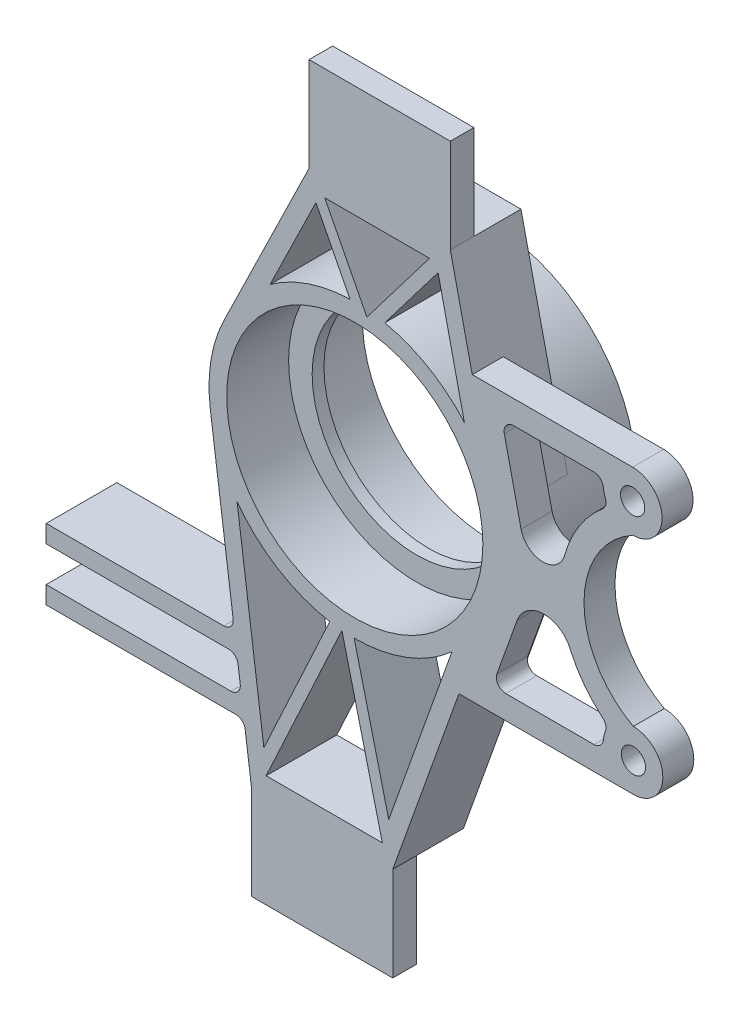
SolidWorks part; units mm, degrees
ref_plane "Front" through (0, 0, 0) normal (0, 0, 1) x (1, 0, 0)
ref_plane "Top" through (0, 0, 0) normal (0, 1, 0) x (1, 0, 0)
ref_plane "Right" through (0, 0, 0) normal (1, 0, 0) x (0, 0, -1)
sketch "Sketch1" plane through (0, 0, 0) normal (0, 0, 1) x (1, 0, 0)
  line L0 (-1549.0237, 297.4698) -> (-1587.1237, 297.4698) construction
  line L2 (-1564.5503, 119.6698) -> (-1602.6503, 119.6698) construction
  line L4 (-1602.6503, 132.3698) -> (-1602.6503, 106.9698)
  line L5 (-1602.6503, 106.9698) -> (-1564.5503, 106.9698)
  line L6 (-1564.5503, 132.3698) -> (-1564.5503, 106.9698)
  line L7 (-1602.6503, 132.3698) -> (-1564.5503, 132.3698)
  line L8 (-1549.0237, 310.1698) -> (-1549.0237, 284.7698)
  line L9 (-1549.0237, 284.7698) -> (-1587.1237, 284.7698)
  line L10 (-1587.1237, 310.1698) -> (-1587.1237, 284.7698)
  line L11 (-1587.1237, 310.1698) -> (-1549.0237, 310.1698)
  line L12 (-1568.0737, 297.4698) -> (-1583.6003, 119.6698) construction
  line L13 (-1587.1237, 284.7698) -> (-1610.118, 237.6971)
  line L14 (-1613.758, 215.2219) -> (-1602.6503, 132.3698)
  line L15 (-1564.5503, 132.3698) -> (-1537.7886, 207.2101)
  line L16 (-1536.4581, 229.099) -> (-1549.0237, 284.7698)
  line L17 (-1585.2805, 277.6924) -> (-1597.6073, 252.4577)
  line L18 (-1576.0758, 259.7306) -> (-1585.2805, 277.6924)
  line L19 (-1552.3332, 277.8017) -> (-1566.7144, 258.9107)
  line L20 (-1545.2328, 246.3443) -> (-1552.3332, 277.8017)
  line L21 (-1599.317, 143.3478) -> (-1606.5457, 197.267)
  line L22 (-1581.5499, 181.7222) -> (-1599.317, 143.3478)
  line L23 (-1565.6496, 143.4402) -> (-1574.9613, 181.1386)
  line L24 (-1548.5876, 191.1547) -> (-1565.6496, 143.4402)
  line L25 (-1577.8052, 186.0317) -> (-1602.6503, 132.3698) construction
  line L26 (-1564.5503, 132.3698) -> (-1577.8052, 186.0317) construction
  line L27 (-1578.2629, 181.2647) -> (-1598.6959, 137.1323)
  line L28 (-1598.6959, 137.1323) -> (-1567.3619, 137.1323)
  line L29 (-1567.3619, 137.1323) -> (-1578.2629, 181.2647)
  line L30 (-1571.5314, 257.8247) -> (-1582.8992, 280.0073)
  line L31 (-1582.8992, 280.0073) -> (-1554.6444, 280.0073)
  line L32 (-1554.6444, 280.0073) -> (-1571.5314, 257.8247)
  line L33 (-1587.1237, 284.7698) -> (-1571.7948, 254.8578) construction
  line L34 (-1571.7948, 254.8578) -> (-1549.0237, 284.7698) construction
  circle A0 centre (-1574.8, 220.4448) radius 34.544
  circle A1 centre (-1574.8, 220.4448) radius 39.3065 construction
  arc A2 (-1610.118, 237.6971) -> (-1613.758, 215.2219) centre (-1574.8, 220.4448) ccw
  arc A3 (-1606.5457, 197.267) -> (-1581.5499, 181.7222) centre (-1574.8, 220.4448) ccw
  arc A4 (-1574.9613, 181.1386) -> (-1548.5876, 191.1547) centre (-1574.8, 220.4448) ccw
  arc A6 (-1537.7886, 207.2101) -> (-1536.4581, 229.099) centre (-1574.8, 220.4448) ccw
  arc A7 (-1545.2328, 246.3443) -> (-1566.7144, 258.9107) centre (-1574.8, 220.4448) ccw
  arc A8 (-1576.0758, 259.7306) -> (-1597.6073, 252.4577) centre (-1574.8, 220.4448) ccw
  point P0 (-1568.0737, 297.4698)
  point P1 (-1583.6003, 119.6698)
  point P3 (-1574.8, 220.4448)
  point P9 (-1568.0737, 297.4698)
  point P12 (-1583.6003, 119.6698)
  point P15 (-1602.6503, 119.6698)
  point P19 (-1564.5503, 119.6698)
  point P20 (-1549.0237, 297.4698)
  point P24 (-1587.1237, 297.4698)
  point P45 (-1571.7948, 254.8578)
  point P47 (-1577.8052, 186.0317)
  point P57 (-1551.1695, 169.79)
  dimension "D3" = 69.088
  dimension "D1" = 38.1
  dimension "D2" = 25.4
  dimension "D4" = 4.7625
  dimension "D5" = 4.7625
  dimension "D6" = 4.7625
  dimension "D7" = 4.7625
  dimension "D8" = 4.7625
  dimension "D9" = 4.7625
  dimension "D10" = 1.5875
  dimension "D11" = 1.5875
  dimension "D12" = 1.5875
  dimension "D13" = 1.5875
  dimension "D14" = 4.7625
  dimension "D15" = 1.5875
  dimension "D16" = 1.5875
  dimension "D17" = 1.5875
  dimension "D18" = 1.5875
extrude "Boss-Extrude1" add sketch "Sketch1" along normal blind 6.35 and the other way blind 12.7 contours L15 A6 L16 L9 L13 A2 L14 L7 L23 A4 L24 L21 A3 L22 L31 L32 L30 L29 L28 L27 A0 L20 A7 L19 L18 A8 L17 | L11 L10 L9 L8 | L7 L4 L5 L6 region at (-1583.6003, 119.6698, 0) region at (-1606.5045, 174.0237, 0) region at (-1568.0737, 297.4698, 0)
sketch "Sketch2" plane through (0, 0, -12.7) normal (0, 0, -1) x (-1, 0, 0)
  line L1 (1549.0237, 310.1698) -> (1587.1237, 310.1698)
  line L2 (1549.0237, 310.1698) -> (1549.0237, 284.7698)
  line L3 (1549.0237, 284.7698) -> (1587.1237, 284.7698)
  line L4 (1587.1237, 310.1698) -> (1587.1237, 284.7698)
  line L5 (1564.5503, 132.3698) -> (1602.6503, 132.3698)
  line L6 (1564.5503, 132.3698) -> (1564.5503, 106.9698)
  line L7 (1564.5503, 106.9698) -> (1602.6503, 106.9698)
  line L8 (1602.6503, 132.3698) -> (1602.6503, 106.9698)
extrude "Cut-Extrude1" cut sketch "Sketch2" against normal up to surface (12.7 mm away) up to plane "Front"
sketch "Sketch3" plane through (0, 0, -12.7) normal (0, 0, -1) x (-1, 0, 0)
  circle A0 centre (1574.8, 220.4448) radius 34.544
  circle A1 centre (1574.8, 220.4448) radius 39.3065
  arc A4 (1613.758, 215.2219) -> (1610.118, 237.6971) centre (1574.8, 220.4448) ccw construction
  circle A5 centre (1574.8, 220.4448) radius 34.544 construction
extrude "Boss-Extrude3" add sketch "Sketch3" along normal offset from surface (17.526 mm away) 36.576 up to face at (-1562.7563, 171.0953, 6.35)
ref_plane "Wheel bearing Mid Plane" through (0, 0, -11.938) normal (0, 0, -1) x (-1, 0, 0)
sketch "Sketch4" plane through (0, 0, -11.938) normal (0, 0, -1) x (-1, 0, 0)
  circle A0 centre (1574.8, 220.4448) radius 28.194
  circle A1 centre (1574.8, 220.4448) radius 34.544
  circle A2 centre (1574.8, 220.4448) radius 34.544 construction
  dimension "D1" = 6.35
extrude "Boss-Extrude4" add sketch "Sketch4" along normal mid plane 3.175
sketch3d "3DSketch30"
  point P0 (-1499.6605, 190.2188, -11.938)
  point P1 (-1499.87, 250.6708, -11.938)
sketch "Sketch12" plane through (0, 0, -11.938) normal (0, 0, -1) x (-1, 0, 0)
  line L0 (1574.8, 248.6388) -> (1574.8, 192.2508) construction
  line L1 (1602.994, 220.4448) -> (1546.606, 220.4448) construction
  line L2 (1574.8, 220.4448) -> (1510.8834, 254.4298) construction
  line L3 (1574.8, 220.4448) -> (1510.8834, 186.4597) construction
  line L4 (1510.8834, 254.4298) -> (1496.306, 262.1808)
  line L5 (1510.8834, 186.4597) -> (1496.306, 178.7088)
  line L6 (1510.8834, 254.4298) -> (1542.1755, 254.4298)
  line L7 (1536.4581, 229.099) -> (1549.0237, 284.7698) construction
  line L8 (1496.306, 262.1808) -> (1543.925, 262.1808)
  line L9 (1496.306, 178.7088) -> (1547.9802, 178.7088)
  line L10 (1564.5503, 132.3698) -> (1537.7886, 207.2101) construction
  line L11 (1510.8834, 186.4597) -> (1545.2086, 186.4597)
  line L12 (26.8478, 175.2501) -> (101.9873, 145.0241)
  circle A0 centre (1574.8, 220.4448) radius 28.194 construction
  circle A1 centre (1574.8, 220.4448) radius 101.6 construction
  arc A2 (1510.8834, 254.4298) -> (1510.8834, 186.4597) centre (1574.8, 220.4448) ccw
  arc A3 (1496.306, 262.1808) -> (1496.306, 178.7088) centre (1574.8, 220.4448) ccw
  dimension "D1" = 203.2
  dimension "D2" = 28
  dimension "D3" = 72.39
  dimension "D4" = 28
  dimension "D5" = 72.39
  dimension "D6" = 16.51
sketch "Sketch16" plane through (0, 0, -11.938) normal (0, 0, -1) x (-1, 0, 0)
  line L0 (1473.2114, 206.0921) -> (1477.0541, 201.975)
  line L1 (1493.6277, 256.6714) -> (1490.0932, 252.8846)
  line L2 (1477.0541, 238.9146) -> (1473.2114, 234.7975)
  line L3 (1507.9155, 220.4448) -> (1487.5955, 220.4448) construction
  line L4 (1477.0541, 238.9146) -> (1477.0541, 252.8846)
  line L5 (1477.0541, 252.8846) -> (1490.0932, 252.8846)
  line L6 (1477.0541, 188.005) -> (1490.0932, 188.005)
  line L7 (1477.0541, 201.975) -> (1477.0541, 188.005)
  line L8 (1490.0932, 188.005) -> (1493.6277, 184.2181)
  line L9 (1499.6605, 250.6708) -> (1499.6605, 190.2188)
  line L11 (1602.994, 220.4448) -> (1546.606, 220.4448) construction
  line L12 (1499.6605, 250.6708) -> (1574.8, 220.4448) construction
  arc A0 (1493.6277, 184.2181) -> (1507.2706, 194.0253) centre (1499.6605, 190.2188) ccw
  arc A1 (1506.6529, 213.3937) -> (1506.6529, 227.4959) centre (1487.5955, 220.4448) ccw
  arc A2 (1507.2706, 246.8643) -> (1493.6277, 256.6714) centre (1499.6605, 250.6708) ccw
  arc A3 (1473.2114, 234.7975) -> (1473.2114, 206.0921) centre (1487.5955, 220.4448) ccw
  spline S0 degree 3 poles (1507.2706, 194.0253) (1506.8889, 194.7187) (1506.243, 196.1544) (1505.3287, 199.2948) (1504.9785, 202.6898) (1505.1113, 206.1293) (1505.4307, 208.6738) (1505.8589, 210.7151) (1506.288, 212.2791) (1506.5252, 213.0215) (1506.6529, 213.3937) knots 0 0 0 0 0.124858 0.249716 0.499432 0.62429 0.749148 0.874006 0.936435 0.998864 0.998864 0.998864 0.998864
  spline S1 degree 3 poles (1506.6529, 227.4959) (1506.5252, 227.868) (1506.288, 228.6104) (1505.8589, 230.1745) (1505.4307, 232.2158) (1505.1113, 234.7602) (1504.9785, 238.1998) (1505.3287, 241.5948) (1506.243, 244.7352) (1506.8889, 246.1709) (1507.2706, 246.8643) knots 0.001136 0.001136 0.001136 0.001136 0.063565 0.125994 0.250852 0.37571 0.500568 0.750284 0.875142 1 1 1 1
sketch "Sketch50" plane through (0, 0, 0) normal (0, 0, 1) x (1, 0, 0)
  line L0 (-1506.3544, 246.093) -> (-1502.6922, 240.9055) construction
  line L1 (-1536.4581, 229.099) -> (-1549.0237, 284.7698) construction
  line L2 (-1535.1787, 252.2583) -> (-1535.1787, 258.6083) construction
  line L3 (-1564.5503, 132.3698) -> (-1537.7886, 207.2101) construction
  line L4 (-1541.3271, 250.6708) -> (-1536.4581, 229.099)
  line L5 (-1543.8644, 190.2188) -> (-1537.7886, 207.2101)
  line L6 (-1499.87, 258.6083) -> (-1543.1187, 258.6083)
  line L7 (-1543.1187, 258.6083) -> (-1541.3271, 250.6708)
  line L8 (-1499.6605, 182.2813) -> (-1546.7028, 182.2813)
  line L9 (-1546.7028, 182.2813) -> (-1543.8644, 190.2188)
  line L10 (-1499.87, 250.6708) -> (-1499.6605, 190.2188) construction
  line L11 (-1535.1787, 252.2583) -> (-1507.6471, 252.2583)
  line L12 (-1535.1787, 252.2583) -> (-1529.9514, 229.099)
  line L13 (-1550.5652, 220.4448) -> (-1448.9652, 220.4448) construction
  line L14 (-1506.3544, 194.7965) -> (-1502.6922, 199.9841) construction
  line L15 (-1535.1787, 252.2583) -> (-1541.3271, 250.6708) construction
  line L16 (-1507.6471, 188.6313) -> (-1537.6883, 188.6313)
  line L17 (-1537.6883, 188.6313) -> (-1537.6883, 182.2813) construction
  line L18 (-1537.6883, 188.6313) -> (-1531.0448, 207.2101)
  line L19 (-1537.6883, 188.6313) -> (-1543.6676, 190.7694) construction
  arc A0 (-1536.4581, 229.099) -> (-1537.7886, 207.2101) centre (-1574.8, 220.4448) cw
  arc A1 (-1499.87, 258.6083) -> (-1499.8425, 242.7333) centre (-1499.87, 250.6708) cw
  arc A2 (-1499.6605, 182.2813) -> (-1499.688, 198.1562) centre (-1499.6605, 190.2188) ccw
  arc A5 (-1499.8425, 242.7333) -> (-1499.688, 198.1562) centre (-1487.5844, 220.487) ccw
  arc A6 (-1499.87, 258.6083) -> (-1507.6471, 252.2583) centre (-1499.87, 250.6708) ccw construction
  arc A7 (-1499.8425, 242.7333) -> (-1506.3544, 246.093) centre (-1499.87, 250.6708) cw construction
  arc A8 (-1499.8425, 198.1562) -> (-1506.3544, 194.7965) centre (-1499.87, 190.2188) ccw construction
  arc A9 (-1506.3544, 246.093) -> (-1518.1428, 229.099) centre (-1487.5844, 220.487) ccw
  arc A10 (-1507.6471, 252.2583) -> (-1506.3544, 246.093) centre (-1499.87, 250.6708) ccw
  arc A11 (-1507.6471, 188.6313) -> (-1506.3544, 194.7965) centre (-1499.87, 190.2188) cw
  arc A12 (-1506.3544, 194.7965) -> (-1516.4987, 207.2101) centre (-1487.5844, 220.487) cw
  arc A13 (-1529.9514, 229.099) -> (-1518.1428, 229.099) centre (-1524.0471, 230.4317) ccw
  arc A14 (-1531.0448, 207.2101) -> (-1516.4987, 207.2101) centre (-1523.7718, 204.6093) cw
  point P35 (-1499.7652, 220.4448)
  dimension "D1" = 7.9375
  dimension "D2" = 6.35
  dimension "D3" = 25.4
extrude "Boss-Extrude10" add sketch "Sketch50" along direction (0, 0, 1) on the side of the normal blind 6.35 and the other way blind 2.0015
hole_wizard "5/16-18 Tapped Hole6" positions "Sketch51" profile "Sketch52" tap size "5/16-18" standard "ANSI Inch" end condition through all
sketch "Sketch51" plane through (0, 0, 6.35) normal (0, 0, 1) x (1, 0, 0)
  point P0 (-1499.87, 250.6708)
  point P3 (-1499.6605, 190.2188)
sketch "Sketch52" plane through (-1499.87, 250.6708, 6.35) normal (1, 0, 0) x (0, -1, 0)
  line L0 (0, 0) -> (0, 36.576)
  line L1 (0, 36.576) -> (3.2639, 36.576)
  line L2 (3.2639, 36.576) -> (3.2639, 0)
  line L5 (3.2639, 0) -> (0, 0)
  line L11 (0, -6.35) -> (0, 107.95) construction
  dimension "Thru Tap Drill Dia." = 6.5278
  dimension "Thru Tap Drill Depth" = 36.576
cosmetic thread "Hole Thread16" parameters "D2"=7.9375
cosmetic thread "Hole Thread17" parameters "D2"=7.9375
fillet "Fillet5" radius 2.54 4 edges at (-1507.6471, 188.6313, 2.1742) (-1506.3544, 194.7965, 2.1742) (-1506.3544, 246.093, 2.1742) (-1507.6471, 252.2583, 2.1742)
fillet "Fillet6" radius 2.54 2 edges at (-1537.6883, 188.6313, 2.1742) (-1535.1787, 252.2583, 2.1742)
ref_plane "Plane3" through (0, 0, 0) normal (0, 0, -1) x (-1, 0, 0)
sketch "rod connection" plane through (0, 0, 0) normal (0, 0, -1) x (-1, 0, 0)
  line L0 (1564.5503, 119.6698) -> (1602.6503, 119.6698) construction
  line L1 (1564.5503, 132.3698) -> (1564.5503, 106.9698) construction
  line L2 (1602.6503, 106.9698) -> (1602.6503, 132.3698) construction
  line L3 (1583.6003, 119.6698) -> (1647.1003, 119.6698) construction
  line L4 (1647.1003, 119.6698) -> (1647.1003, 156.8834) construction
  line L5 (1583.6003, 119.6698) -> (1647.1003, 156.8834) construction
  line L6 (1583.6003, 119.6698) -> (1583.6003, 156.8834) construction
  line L7 (1583.6003, 156.8834) -> (1647.1003, 156.8834) construction
  line L8 (1647.1003, 161.6459) -> (1606.5752, 161.6459)
  line L9 (1607.2137, 166.4084) -> (1658.0137, 166.4084)
  line L10 (1647.1003, 152.1209) -> (1647.1003, 161.6459) construction
  line L11 (1613.758, 215.2219) -> (1602.6503, 132.3698) construction
  line L12 (1647.1003, 152.1209) -> (1605.2983, 152.1209)
  line L13 (1647.1003, 161.6459) -> (1647.1003, 166.4084) construction
  line L14 (1647.1003, 152.1209) -> (1647.1003, 147.3584) construction
  line L15 (1604.6598, 147.3584) -> (1658.0137, 147.3584)
  line L16 (1647.1003, 161.6459) -> (1658.0137, 161.6459)
  line L17 (1658.0137, 166.4084) -> (1658.0137, 161.6459)
  line L18 (1647.1003, 152.1209) -> (1658.0137, 152.1209)
  line L19 (1658.0137, 147.3584) -> (1658.0137, 152.1209)
  line L20 (1658.0137, 161.6459) -> (1658.0137, 152.1209) construction
  line L21 (1607.2137, 166.4084) -> (1606.5752, 161.6459)
  line L22 (1605.2983, 152.1209) -> (1604.6598, 147.3584)
  point P6 (1583.6003, 119.6698)
  point P17 (1647.1003, 156.8834)
  dimension "D1" = 63.5
  dimension "D2" = 37.2136
  dimension "D3" = 9.525
  dimension "D4" = 4.7625
  dimension "D5" = 4.7625
  dimension "D6" = 50.8
extrude "Boss-Extrude9" add sketch "rod connection" against normal blind 6.35 and the other way blind 12.7
ref_plane "Plane5" through (0, 166.4084, 0) normal (0, 1, 0) x (1, 0, 0)
sketch "ackerman adjustment hole positoins" plane through (0, 166.4084, 0) normal (0, 1, 0) x (1, 0, 0)
  line L0 (-1647.1003, 0) -> (-1621.7003, 0) construction
  line L2 (-1647.1003, 0) -> (-1647.1003, 6.35) construction
  line L3 (-1647.1003, 6.35) -> (-1621.7003, 6.35) construction
  line L4 (-1647.1003, 6.35) -> (-1659.8003, 6.35) construction
  line L5 (-1647.1003, 0) -> (-1659.8003, 0) construction
  line L6 (-1659.8003, 0) -> (-1659.8003, 6.35) construction
  line L7 (-1621.7003, 0) -> (-1621.7003, 6.35) construction
  point P0 (-1647.1003, 0)
  point P3 (-1634.4003, 6.35)
  point P7 (-1647.1003, 0)
  dimension "D1" = 12.7
  dimension "D2" = 6.35
  dimension "D3" = 25.4
fillet "Fillet4" radius 2.54 4 edges at (-1607.2137, 166.4084, -3.175) (-1606.5752, 161.6459, -3.175) (-1605.2983, 152.1209, -3.175) (-1604.6598, 147.3584, -3.175)
equation "\"outer support width\"= 0.1875in"
equation "\"inner support width\"= 0.125in"
equation "\"D4@Sketch1\"=\"outer support width\""
equation "\"D5@Sketch1\"=\"outer support width\""
equation "\"D6@Sketch1\"=\"outer support width\""
equation "\"D7@Sketch1\"=\"outer support width\""
equation "\"D8@Sketch1\"=\"outer support width\""
equation "\"D9@Sketch1\"=\"outer support width\""
equation "\"D10@Sketch1\"=\"inner support width\"/2"
equation "\"D11@Sketch1\"=\"inner support width\"/2"
equation "\"D12@Sketch1\"=\"inner support width\"/2"
equation "\"D13@Sketch1\"=\"inner support width\"/2"
equation "\"D14@Sketch1\"=\"outer support width\""
equation "\"D15@Sketch1\"=\"inner support width\"/2"
equation "\"D16@Sketch1\"=\"inner support width\"/2"
equation "\"D17@Sketch1\"=\"inner support width\"/2"
equation "\"D18@Sketch1\"=\"inner support width\"/2"
